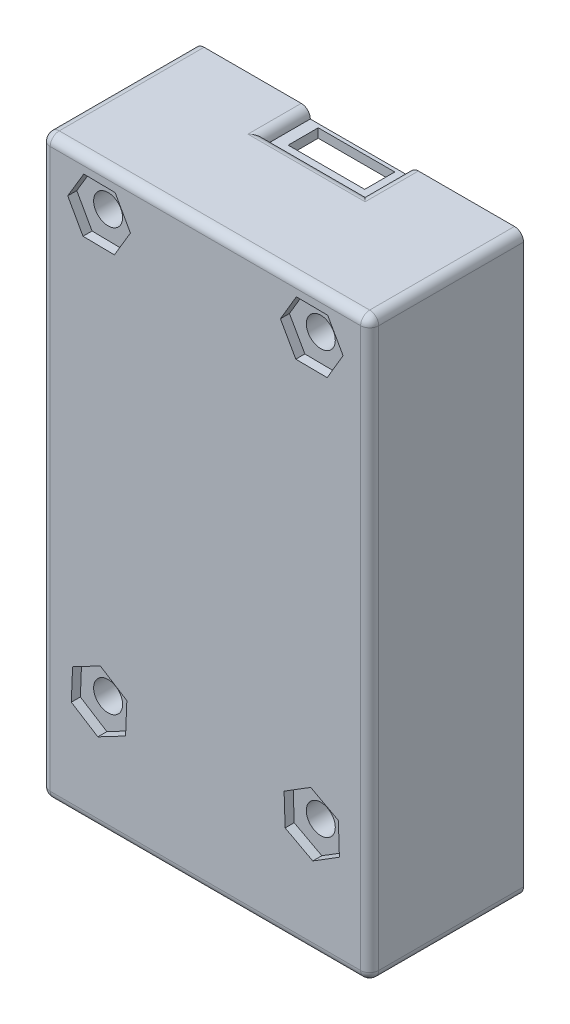
SolidWorks part; units mm, degrees
ref_plane "Alzado" through (0, 0, 0) normal (0, 0, 1) x (1, 0, 0)
ref_plane "Planta" through (0, 0, 0) normal (0, 1, 0) x (1, 0, 0)
ref_plane "Vista lateral" through (0, 0, 0) normal (1, 0, 0) x (0, 0, -1)
sketch "Croquis1" plane through (0, 0, 0) normal (0, 0, 1) x (1, 0, 0)
  line L0 (-9.715, 23.9209) -> (-9.715, -24.2791) construction
  line L1 (-13.715, 27.9209) -> (22.585, 27.9209)
  line L2 (-13.715, 27.9209) -> (-13.715, -35.7791)
  line L3 (-13.715, -35.7791) -> (22.585, -35.7791)
  line L4 (22.585, 27.9209) -> (22.585, -35.7791)
  line L5 (18.585, -24.2791) -> (18.585, 23.9209) construction
  line L6 (-8.215, -25.7791) -> (17.085, -25.7791) construction
  line L7 (17.085, 25.4209) -> (-8.215, 25.4209) construction
  dimension "D1" = 4
  dimension "D2" = 4
  dimension "D3" = 10
  dimension "D4" = 2.5
extrude "Saliente-Extruir1" add sketch "Croquis1" along normal blind 2
sketch "Croquis2" plane through (0, 0, 0) normal (0, 0, -1) x (-1, 0, 0)
  circle A0 centre (-16.185, 23.1209) radius 1.45
  circle A1 centre (7.315, 23.1209) radius 1.45
  circle A2 centre (7.315, -23.4791) radius 1.45
  circle A3 centre (-16.185, -23.4791) radius 1.45
extrude "Cortar-Extruir1" cut sketch "Croquis2" against normal through all
sketch "Croquis3" plane through (0, 0, 0) normal (0, 0, -1) x (-1, 0, 0)
  line L1 (-22.585, 27.9209) -> (13.715, 27.9209)
  line L2 (-22.585, 27.9209) -> (-22.585, -35.7791)
  line L3 (-22.585, -35.7791) -> (13.715, -35.7791)
  line L4 (13.715, 27.9209) -> (13.715, -35.7791)
  line L5 (-20.585, 25.9209) -> (11.715, 25.9209)
  line L6 (-20.585, 25.9209) -> (-20.585, -33.7791)
  line L7 (-20.585, -33.7791) -> (11.715, -33.7791)
  line L8 (11.715, 25.9209) -> (11.715, -33.7791)
  dimension "D1" = 2
  dimension "D2" = 2
  dimension "D3" = 2
  dimension "D4" = 2
extrude "Saliente-Extruir2" add sketch "Croquis3" along normal blind 15
sketch "Croquis4" plane through (0, 27.9209, 0) normal (0, 1, 0) x (1, 0, 0)
  line L0 (-3.115, 14.6) -> (12.285, 14.6) construction
  line L1 (8.76, 11.2777) -> (0.3018, 11.2777)
  line L2 (8.76, 11.2777) -> (8.76, 14.6)
  line L3 (8.76, 14.6) -> (0.3018, 14.6)
  line L4 (0.3018, 11.2777) -> (0.3018, 14.6)
extrude "Cortar-Extruir2" cut sketch "Croquis4" against normal blind 15
sketch "Croquis5" plane through (0, 27.9209, 0) normal (0, 1, 0) x (1, 0, 0)
  line L0 (-13.715, 15) -> (22.585, 15) construction
  line L1 (-0.9754, 15) -> (9.9722, 15)
  line L2 (-0.9754, 15) -> (-0.9754, 10.1104)
  line L3 (-0.9754, 10.1104) -> (9.9722, 10.1104)
  line L4 (9.9722, 15) -> (9.9722, 10.1104)
extrude "Cortar-Extruir3" cut sketch "Croquis5" against normal blind 1
sketch "Croquis6" plane through (0, 0, 0) normal (0, 0, -1) x (-1, 0, 0)
  circle A0 centre (-16.185, 23.1209) radius 2.4
  circle A1 centre (7.315, 23.1209) radius 2.4
  circle A2 centre (7.315, -23.4791) radius 2.4
  circle A3 centre (-16.185, -23.4791) radius 2.4
extrude "Saliente-Extruir3" add sketch "Croquis6" along normal blind 10
fillet "Redondeo1" radius 1 11 edges at (-0.9754, 27.9209, -12.5552) (4.4984, 27.9209, -10.1104) (9.9722, 27.9209, -12.5552) (22.585, -3.9291, 2) (22.585, -35.7791, -6.5) (4.435, -35.7791, 2) (-13.715, -35.7791, -6.5) (-13.715, -3.9291, 2) (4.435, 27.9209, 2) (-13.715, 27.9209, -6.5) (22.585, 27.9209, -6.5)
sketch "Croquis7" plane through (0, 0, 2) normal (0, 0, 1) x (1, 0, 0)
  line L1 (-5.6269, 20.0959) -> (-3.8512, 23.0704)
  line L2 (-3.8512, 23.0704) -> (-5.5394, 26.0953)
  line L3 (-5.5394, 26.0953) -> (-9.0031, 26.1458)
  line L4 (-9.0031, 26.1458) -> (-10.7787, 23.1714)
  line L5 (-10.7787, 23.1714) -> (-9.0906, 20.1465)
  line L6 (-9.0906, 20.1465) -> (-5.6269, 20.0959)
  line L7 (17.8872, 20.1038) -> (19.649, 23.0865)
  line L8 (19.649, 23.0865) -> (17.9468, 26.1035)
  line L9 (17.9468, 26.1035) -> (14.4828, 26.1379)
  line L10 (14.4828, 26.1379) -> (12.7211, 23.1553)
  line L11 (12.7211, 23.1553) -> (14.4233, 20.1382)
  line L12 (14.4233, 20.1382) -> (17.8872, 20.1038)
  line L13 (-4.3866, -25.3297) -> (-4.2482, -21.8683)
  line L14 (-4.2482, -21.8683) -> (-7.1766, -20.0178)
  line L15 (-7.1766, -20.0178) -> (-10.2434, -21.6286)
  line L16 (-10.2434, -21.6286) -> (-10.3818, -25.0899)
  line L17 (-10.3818, -25.0899) -> (-7.4534, -26.9405)
  line L18 (-7.4534, -26.9405) -> (-4.3866, -25.3297)
  line L19 (19.2404, -25.1114) -> (19.1263, -21.6492)
  line L20 (19.1263, -21.6492) -> (16.0709, -20.0169)
  line L21 (16.0709, -20.0169) -> (13.1296, -21.8468)
  line L22 (13.1296, -21.8468) -> (13.2437, -25.309)
  line L23 (13.2437, -25.309) -> (16.2991, -26.9413)
  line L24 (16.2991, -26.9413) -> (19.2404, -25.1114)
  circle A0 centre (-7.315, 23.1209) radius 3 construction
  circle A1 centre (16.185, 23.1209) radius 3 construction
  circle A2 centre (-7.315, -23.4791) radius 3 construction
  circle A3 centre (16.185, -23.4791) radius 3 construction
  point P1 (-7.2712, 26.1206)
  dimension "D1" = 6
  dimension "D2" = 6
  dimension "D3" = 6
  dimension "D4" = 6
extrude "Cortar-Extruir4" cut sketch "Croquis7" against normal blind 1
sketch "Croquis8" plane through (0, 0, 0) normal (0, 0, -1) x (-1, 0, 0)
  circle A0 centre (-16.185, 23.1209) radius 1.6
  circle A1 centre (7.315, 23.1209) radius 1.6
  circle A2 centre (-16.185, -23.4791) radius 1.6
  circle A3 centre (7.315, -23.4791) radius 1.6
  dimension "D1" = 3.2
  dimension "D2" = 3.2
  dimension "D3" = 3.2
  dimension "D4" = 3.2
extrude "Cortar-Extruir5" cut sketch "Croquis8" against normal through all both and the other way through all
